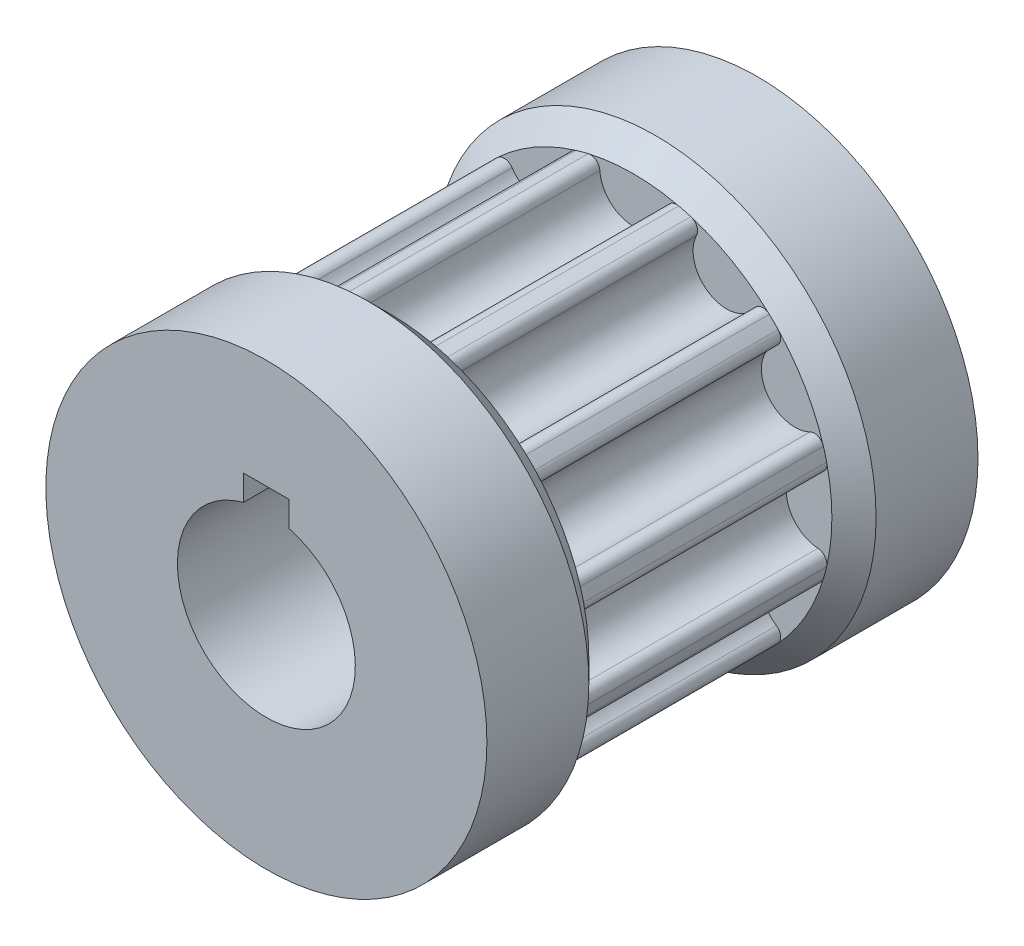
SolidWorks part; units mm, degrees
material "Nailon 6/10"
ref_plane "Alzado" through (0, 0, 0) normal (0, 0, 1) x (1, 0, 0)
ref_plane "Planta" through (0, 0, 0) normal (0, 1, 0) x (1, 0, 0)
ref_plane "Vista lateral" through (0, 0, 0) normal (1, 0, 0) x (0, 0, -1)
sketch "Croquis3" plane through (0, 0, 0) normal (0, 0, 1) x (1, 0, 0)
  line L0 (0, 0) -> (0, 8.98) construction
  line L1 (0, 0) -> (4.49, 7.7769) construction
  circle A0 centre (0, 0) radius 8.98 construction
  circle A1 centre (0, 0) radius 6.92 construction
  circle A2 centre (0, 8.445) radius 1.525 construction
  circle A3 centre (1.9513, 8.3244) radius 0.43 construction
  circle A4 centre (4.2225, 7.3136) radius 1.525 construction
  circle A5 centre (2.4723, 8.1847) radius 0.43 construction
  arc A6 (0, 6.92) -> (1.5221, 8.3509) centre (0, 8.445) ccw
  arc A7 (1.5221, 8.3509) -> (2.0494, 8.743) centre (1.9513, 8.3244) cw
  arc A8 (2.0494, 8.743) -> (2.5967, 8.5964) centre (0, 0) cw
  arc A9 (2.5967, 8.5964) -> (2.8573, 7.9931) centre (2.4723, 8.1847) cw
  arc A10 (2.8573, 7.9931) -> (3.46, 5.9929) centre (4.2225, 7.3136) ccw
  arc A11 (6.471, 5.4936) -> (5.9929, 3.46) centre (7.3136, 4.2225) ccw
  arc A12 (6.547, 6.1463) -> (6.471, 5.4936) centre (6.2335, 5.852) cw
  arc A13 (6.1463, 6.547) -> (6.547, 6.1463) centre (0, 0) cw
  arc A14 (5.4936, 6.471) -> (6.1463, 6.547) centre (5.852, 6.2335) cw
  arc A15 (3.46, 5.9929) -> (5.4936, 6.471) centre (4.2225, 7.3136) ccw
  arc A16 (8.3509, 1.5221) -> (6.92, 0) centre (8.445, 0) ccw
  arc A17 (8.743, 2.0494) -> (8.3509, 1.5221) centre (8.3244, 1.9513) cw
  arc A18 (8.5964, 2.5967) -> (8.743, 2.0494) centre (0, 0) cw
  arc A19 (7.9931, 2.8573) -> (8.5964, 2.5967) centre (8.1847, 2.4723) cw
  arc A20 (5.9929, 3.46) -> (7.9931, 2.8573) centre (7.3136, 4.2225) ccw
  arc A21 (7.9931, -2.8573) -> (5.9929, -3.46) centre (7.3136, -4.2225) ccw
  arc A22 (8.5964, -2.5967) -> (7.9931, -2.8573) centre (8.1847, -2.4723) cw
  arc A23 (8.743, -2.0494) -> (8.5964, -2.5967) centre (0, 0) cw
  arc A24 (8.3509, -1.5221) -> (8.743, -2.0494) centre (8.3244, -1.9513) cw
  arc A25 (6.92, 0) -> (8.3509, -1.5221) centre (8.445, 0) ccw
  arc A26 (5.4936, -6.471) -> (3.46, -5.9929) centre (4.2225, -7.3136) ccw
  arc A27 (6.1463, -6.547) -> (5.4936, -6.471) centre (5.852, -6.2335) cw
  arc A28 (6.547, -6.1463) -> (6.1463, -6.547) centre (0, 0) cw
  arc A29 (6.471, -5.4936) -> (6.547, -6.1463) centre (6.2335, -5.852) cw
  arc A30 (5.9929, -3.46) -> (6.471, -5.4936) centre (7.3136, -4.2225) ccw
  arc A31 (1.5221, -8.3509) -> (0, -6.92) centre (0, -8.445) ccw
  arc A32 (2.0494, -8.743) -> (1.5221, -8.3509) centre (1.9513, -8.3244) cw
  arc A33 (2.5967, -8.5964) -> (2.0494, -8.743) centre (0, 0) cw
  arc A34 (2.8573, -7.9931) -> (2.5967, -8.5964) centre (2.4723, -8.1847) cw
  arc A35 (3.46, -5.9929) -> (2.8573, -7.9931) centre (4.2225, -7.3136) ccw
  arc A36 (-2.8573, -7.9931) -> (-3.46, -5.9929) centre (-4.2225, -7.3136) ccw
  arc A37 (-2.5967, -8.5964) -> (-2.8573, -7.9931) centre (-2.4723, -8.1847) cw
  arc A38 (-2.0494, -8.743) -> (-2.5967, -8.5964) centre (0, 0) cw
  arc A39 (-1.5221, -8.3509) -> (-2.0494, -8.743) centre (-1.9513, -8.3244) cw
  arc A40 (0, -6.92) -> (-1.5221, -8.3509) centre (0, -8.445) ccw
  arc A41 (-6.471, -5.4936) -> (-5.9929, -3.46) centre (-7.3136, -4.2225) ccw
  arc A42 (-6.547, -6.1463) -> (-6.471, -5.4936) centre (-6.2335, -5.852) cw
  arc A43 (-6.1463, -6.547) -> (-6.547, -6.1463) centre (0, 0) cw
  arc A44 (-5.4936, -6.471) -> (-6.1463, -6.547) centre (-5.852, -6.2335) cw
  arc A45 (-3.46, -5.9929) -> (-5.4936, -6.471) centre (-4.2225, -7.3136) ccw
  arc A46 (-8.3509, -1.5221) -> (-6.92, 0) centre (-8.445, 0) ccw
  arc A47 (-8.743, -2.0494) -> (-8.3509, -1.5221) centre (-8.3244, -1.9513) cw
  arc A48 (-8.5964, -2.5967) -> (-8.743, -2.0494) centre (0, 0) cw
  arc A49 (-7.9931, -2.8573) -> (-8.5964, -2.5967) centre (-8.1847, -2.4723) cw
  arc A50 (-5.9929, -3.46) -> (-7.9931, -2.8573) centre (-7.3136, -4.2225) ccw
  arc A51 (-7.9931, 2.8573) -> (-5.9929, 3.46) centre (-7.3136, 4.2225) ccw
  arc A52 (-8.5964, 2.5967) -> (-7.9931, 2.8573) centre (-8.1847, 2.4723) cw
  arc A53 (-8.743, 2.0494) -> (-8.5964, 2.5967) centre (0, 0) cw
  arc A54 (-8.3509, 1.5221) -> (-8.743, 2.0494) centre (-8.3244, 1.9513) cw
  arc A55 (-6.92, 0) -> (-8.3509, 1.5221) centre (-8.445, 0) ccw
  arc A56 (-5.4936, 6.471) -> (-3.46, 5.9929) centre (-4.2225, 7.3136) ccw
  arc A57 (-6.1463, 6.547) -> (-5.4936, 6.471) centre (-5.852, 6.2335) cw
  arc A58 (-6.547, 6.1463) -> (-6.1463, 6.547) centre (0, 0) cw
  arc A59 (-6.471, 5.4936) -> (-6.547, 6.1463) centre (-6.2335, 5.852) cw
  arc A60 (-5.9929, 3.46) -> (-6.471, 5.4936) centre (-7.3136, 4.2225) ccw
  arc A61 (-1.5221, 8.3509) -> (0, 6.92) centre (0, 8.445) ccw
  arc A62 (-2.0494, 8.743) -> (-1.5221, 8.3509) centre (-1.9513, 8.3244) cw
  arc A63 (-2.5967, 8.5964) -> (-2.0494, 8.743) centre (0, 0) cw
  arc A64 (-2.8573, 7.9931) -> (-2.5967, 8.5964) centre (-2.4723, 8.1847) cw
  arc A65 (-3.46, 5.9929) -> (-2.8573, 7.9931) centre (-4.2225, 7.3136) ccw
  dimension "D1" = 17.96
  dimension "D2" = 13.84
  dimension "D3" = 3.05
  dimension "D4" = 0.86
  dimension "D5" = 30
  dimension "D6" = 12
extrude "Saliente-Extruir1" add sketch "Croquis3" along normal mid plane 11 contours A65 A56 A57 A58 A59 A60 A51 A52 A53 A54 A55 A46 A47 A48 A49 A50 A41 A42 A43 A44 A45 A36 A37 A38 A39 A40 A31 A32 A33 A34 A35 A26 A27 A28 A29 A30 A21 A22 A23 A24 A25 A16 A17 A18 A19 A20 A11 A12 A13 A14 A15 region at (0, 0, 0)
sketch "Croquis5" plane through (0, 0, 5.5) normal (0, 0, 1) x (1, 0, 0)
  circle A0 centre (0, 0) radius 8.98
  arc A1 (2.5967, 8.5964) -> (2.0494, 8.743) centre (0, 0) ccw construction
extrude "Saliente-Extruir2" add sketch "Croquis5" along normal blind 1 draft 45 draft outward yes
sketch "Croquis8" plane through (0, 0, 6.5) normal (0, 0, 1) x (1, 0, 0)
  circle A0 centre (0, 0) radius 9.98 construction
  circle A1 centre (0, 0) radius 9.98
extrude "Saliente-Extruir3" add sketch "Croquis8" along normal blind 4.6125
mirror "Simetría1" about plane through (0, 0, 0) normal (0, 0, 1) of "Saliente-Extruir3", "Saliente-Extruir2"
sketch "Croquis6" plane through (0, 0, 11.1125) normal (0, 0, 1) x (1, 0, 0)
  line L2 (-1.035, 3.8897) -> (-1.035, 5.04)
  line L3 (-1.035, 5.04) -> (1.035, 5.04)
  line L4 (1.035, 3.8897) -> (1.035, 5.04)
  arc A0 (-1.035, 3.8897) -> (1.035, 3.8897) centre (0, 0) ccw
  point P8 (1.035, 4.4648)
  point P9 (0, 5.04)
  dimension "D1" = 8.05
  dimension "D2" = 2.07
  dimension "D3" = 5.04
extrude "Cortar-Extruir1" cut sketch "Croquis6" against normal through all
equation "\"X\"= 17.96"
equation "\"N\"= 12"
equation "\"D1@Croquis3\"=\"X\""
equation "\"Y\"= \"X\" - 2 * 2.06"
equation "\"A\"= 360 / \"N\""
equation "\"D2@Croquis3\"=\"Y\""
equation "\"D5@Croquis3\"=\"A\""
equation "\"D6@Croquis3\"=\"N\""
